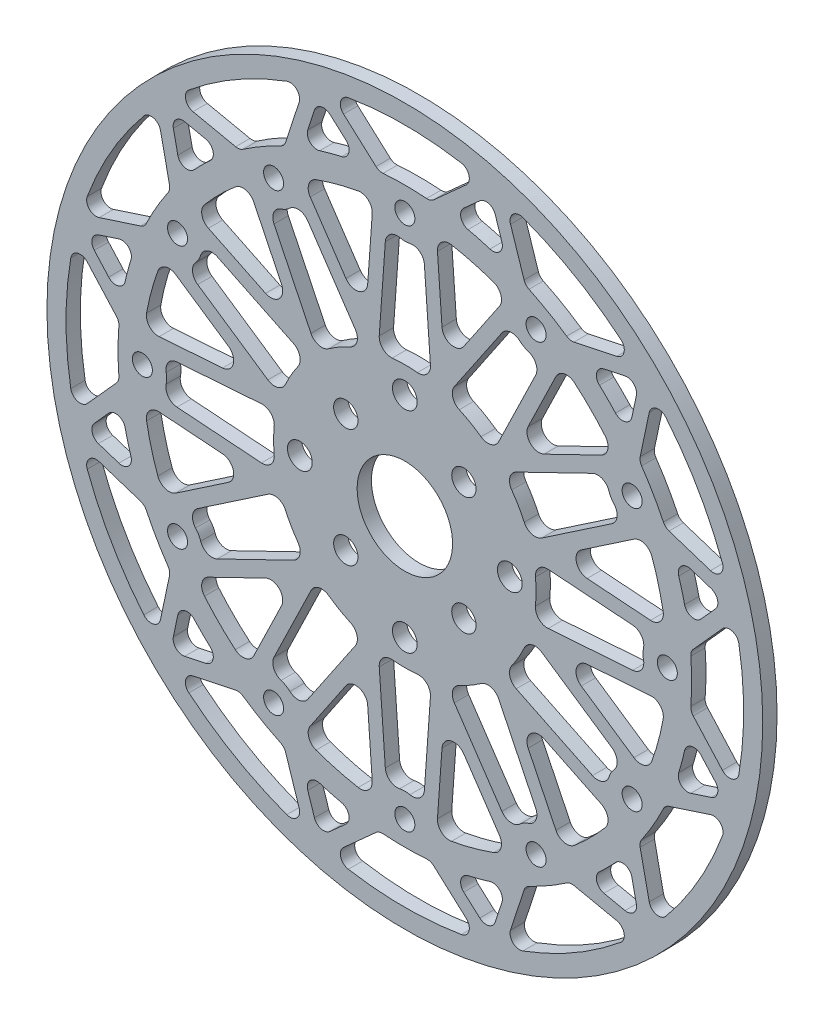
SolidWorks part; units mm, degrees
material "Thornel Mat VMA"
ref_plane "前视基准面" through (0, 0, 0) normal (0, 0, 1) x (1, 0, 0)
ref_plane "上视基准面" through (0, 0, 0) normal (0, 1, 0) x (1, 0, 0)
ref_plane "右视基准面" through (0, 0, 0) normal (1, 0, 0) x (0, 0, -1)
other "Configuration Table"
sketch "草图1" plane through (0, 0, 0) normal (0, 0, 1) x (1, 0, 0)
  circle A0 centre (0, 0) radius 75
  dimension "D1" = 150
extrude "凸台-拉伸1" add sketch "草图1" along normal blind 3
sketch "草图2" plane through (0, 0, 0) normal (0, 0, -1) x (-1, 0, 0)
  line L0 (0, 22) -> (0, 0) construction
  line L1 (0, 0) -> (12.3744, 12.3744) construction
  circle A0 centre (0, 0) radius 55 construction
  circle A1 centre (0, 55) radius 2.1
  circle A2 centre (27.5, 47.6314) radius 2.1
  circle A3 centre (47.6314, 27.5) radius 2.1
  circle A4 centre (55, 0) radius 2.1
  circle A5 centre (47.6314, -27.5) radius 2.1
  circle A6 centre (27.5, -47.6314) radius 2.1
  circle A7 centre (0, -55) radius 2.1
  circle A8 centre (-27.5, -47.6314) radius 2.1
  circle A9 centre (-47.6314, -27.5) radius 2.1
  circle A10 centre (-55, 0) radius 2.1
  circle A11 centre (-47.6314, 27.5) radius 2.1
  circle A12 centre (-27.5, 47.6314) radius 2.1
  circle A13 centre (0, 0) radius 22 construction
  circle A14 centre (0, 0) radius 17.5 construction
  circle A15 centre (0, 22) radius 2.6
  circle A16 centre (12.3744, 12.3744) radius 2.55
  circle A17 centre (22, 0) radius 2.6
  circle A18 centre (12.3744, -12.3744) radius 2.55
  circle A19 centre (0, -22) radius 2.6
  circle A20 centre (-12.3744, -12.3744) radius 2.55
  circle A21 centre (-22, 0) radius 2.6
  circle A22 centre (-12.3744, 12.3744) radius 2.55
  circle A23 centre (0, 0) radius 10
  point P29 (0, 0)
  point P49 (0, 0)
  dimension "D1" = 110
  dimension "D2" = 4.2
  dimension "D4" = 35
  dimension "D5" = 44
  dimension "D6" = 5.2
  dimension "D8" = 5.1
  dimension "D10" = 20
  dimension "D7" = 45
  dimension "D3" = 12
  dimension "D9" = 4
extrude "切除-拉伸1" cut sketch "草图2" against normal blind 3
sketch "草图3" plane through (0, 0, 3) normal (0, 0, 1) x (1, 0, 0)
  line L0 (0, 55) -> (0, -55)
  line L1 (-27.5, 47.6314) -> (27.5, -47.6314)
  line L2 (-27.5, -47.6314) -> (27.5, 47.6314)
  line L3 (-55, 0) -> (55, 0)
  line L4 (-47.6314, 27.5) -> (47.6314, -27.5)
  line L5 (-47.6314, -27.5) -> (47.6314, 27.5)
  circle A0 centre (0, 0) radius 27.5
  circle A1 centre (-47.6314, 27.5) radius 2.1 construction
  circle A2 centre (-55, 0) radius 2.1 construction
  circle A3 centre (-47.6314, -27.5) radius 2.1 construction
  circle A4 centre (-27.5, -47.6314) radius 2.1 construction
  circle A5 centre (0, -55) radius 2.1 construction
  circle A6 centre (27.5, -47.6314) radius 2.1 construction
  circle A7 centre (47.6314, -27.5) radius 2.1 construction
  circle A8 centre (55, 0) radius 2.1 construction
  circle A9 centre (47.6314, 27.5) radius 2.1 construction
  circle A10 centre (27.5, 47.6314) radius 2.1 construction
  circle A11 centre (0, 55) radius 2.1 construction
  circle A12 centre (-27.5, 47.6314) radius 2.1 construction
  circle A13 centre (-47.6314, 27.5) radius 2.1
  circle A14 centre (-55, 0) radius 2.1
  circle A15 centre (-47.6314, -27.5) radius 2.1
  circle A16 centre (-27.5, -47.6314) radius 2.1
  circle A17 centre (0, -55) radius 2.1
  circle A18 centre (27.5, -47.6314) radius 2.1
  circle A19 centre (47.6314, -27.5) radius 2.1
  circle A20 centre (55, 0) radius 2.1
  circle A21 centre (47.6314, 27.5) radius 2.1
  circle A22 centre (27.5, 47.6314) radius 2.1
  circle A23 centre (0, 55) radius 2.1
  circle A24 centre (-27.5, 47.6314) radius 2.1
  circle A25 centre (-27.5, 47.6314) radius 5.1
  circle A26 centre (0, 55) radius 5.1
  circle A27 centre (27.5, 47.6314) radius 5.1
  circle A28 centre (47.6314, 27.5) radius 5.1
  circle A29 centre (55, 0) radius 5.1
  circle A30 centre (47.6314, -27.5) radius 5.1
  circle A31 centre (27.5, -47.6314) radius 5.1
  circle A32 centre (0, -55) radius 5.1
  circle A33 centre (-27.5, -47.6314) radius 5.1
  circle A34 centre (-47.6314, -27.5) radius 5.1
  circle A35 centre (-55, 0) radius 5.1
  circle A36 centre (-47.6314, 27.5) radius 5.1
  circle A37 centre (0, 0) radius 55
  dimension "D1" = 55
  dimension "D2" = 3
extrude "切除-拉伸2" cut sketch "草图3" against normal blind 10 contours A26 A37 A25 L1 A0 L0 | A27 A37 A26 L0 A0 L2 | A28 A37 A27 L2 A0 L5 | A29 A37 A28 L5 A0 L3 | A30 A37 A29 L3 A0 L4 | A31 A37 A30 L4 A0 L1 | A32 A37 A31 L1 A0 L0 | A33 A37 A32 L0 A0 L2 | A34 A37 A33 L2 A0 L5 | A35 A37 A34 L5 A0 L3 | A36 A37 A35 L3 A0 L4 | A25 A37 A36 L4 A0 L1 region at (10.7724, 40.2033, 3) region at (-10.7724, 40.2033, 3) region at (29.4309, 29.4309, 3) region at (-29.4309, 29.4309, 3) region at (10.7724, -40.2033, 3) region at (-10.7724, -40.2033, 3) region at (29.4309, -29.4309, 3) region at (-29.4309, -29.4309, 3) region at (-40.2033, -10.7724, 3) region at (-40.2033, 10.7724, 3) region at (40.2033, 10.7724, 3) region at (40.2033, -10.7724, 3)
sketch "草图4" plane through (0, 0, 3) normal (0, 0, 1) x (1, 0, 0)
  line L0 (-14.235, 53.1259) -> (0, 0) construction
  line L1 (-5.0945, 54.7635) -> (-7.1175, 26.563)
  line L2 (-22.9698, 49.9739) -> (-7.1175, 26.563)
  line L3 (5.0945, 54.7635) -> (7.1175, 26.563)
  line L4 (22.9698, 49.9739) -> (7.1175, 26.563)
  line L5 (31.7938, 44.8794) -> (19.4454, 19.4454)
  line L6 (44.8794, 31.7938) -> (19.4454, 19.4454)
  line L7 (49.9739, 22.9698) -> (26.563, 7.1175)
  line L8 (54.7635, 5.0945) -> (26.563, 7.1175)
  line L9 (54.7635, -5.0945) -> (26.563, -7.1175)
  line L10 (49.9739, -22.9698) -> (26.563, -7.1175)
  line L11 (44.8794, -31.7938) -> (19.4454, -19.4454)
  line L12 (31.7938, -44.8794) -> (19.4454, -19.4454)
  line L13 (22.9698, -49.9739) -> (7.1175, -26.563)
  line L14 (5.0945, -54.7635) -> (7.1175, -26.563)
  line L15 (-5.0945, -54.7635) -> (-7.1175, -26.563)
  line L16 (-22.9698, -49.9739) -> (-7.1175, -26.563)
  line L17 (-31.7938, -44.8794) -> (-19.4454, -19.4454)
  line L18 (-44.8794, -31.7938) -> (-19.4454, -19.4454)
  line L19 (-49.9739, -22.9698) -> (-26.563, -7.1175)
  line L20 (-54.7635, -5.0945) -> (-26.563, -7.1175)
  line L21 (-54.7635, 5.0945) -> (-26.563, 7.1175)
  line L22 (-49.9739, 22.9698) -> (-26.563, 7.1175)
  line L23 (-44.8794, 31.7938) -> (-19.4454, 19.4454)
  line L24 (-31.7938, 44.8794) -> (-19.4454, 19.4454)
  line L25 (0, 0) -> (-7.1175, 26.563) construction
  arc A0 (-5.0945, 54.7635) -> (-22.9698, 49.9739) centre (0, 0) ccw construction
  dimension "D2" = 27.5
  dimension "D1" = 12
extrude "拉伸-薄壁1" add sketch "草图4" against normal blind 3 thin thin type mid plane wall 3
fillet "圆角1" radius 2.5 84 edges at (21.5762, 50.5912, 1.5) (8.3038, 30.9902, 1.5) (6.61, 54.6014, 1.5) (5.5876, 26.9264, 1.5) (-3.8164, 51.6169, 1.5) (3.8164, 51.6169, 1.5) (43.9812, 33.0251, 1.5) (22.6864, 22.6864, 1.5) (33.0251, 43.9812, 1.5) (8.6242, 26.1127, 1.5) (22.5034, 46.6098, 1.5) (29.1136, 42.7934, 1.5) (18.3022, 20.5251, 1.5) (54.6014, 6.61, 1.5) (30.9902, 8.3038, 1.5) (50.5912, 21.5762, 1.5) (20.5251, 18.3022, 1.5) (42.7934, 29.1136, 1.5) (46.6098, 22.5034, 1.5) (26.1127, 8.6242, 1.5) (50.5912, -21.5762, 1.5) (30.9902, -8.3038, 1.5) (54.6014, -6.61, 1.5) (26.9264, 5.5876, 1.5) (51.6169, 3.8164, 1.5) (51.6169, -3.8164, 1.5) (26.9264, -5.5876, 1.5) (33.0251, -43.9812, 1.5) (22.6864, -22.6864, 1.5) (43.9812, -33.0251, 1.5) (26.1127, -8.6242, 1.5) (46.6098, -22.5034, 1.5) (42.7934, -29.1136, 1.5) (20.5251, -18.3022, 1.5) (6.61, -54.6014, 1.5) (8.3038, -30.9902, 1.5) (21.5762, -50.5912, 1.5) (18.3022, -20.5251, 1.5) (29.1136, -42.7934, 1.5) (22.5034, -46.6098, 1.5) (8.6242, -26.1127, 1.5) (-21.5762, -50.5912, 1.5) (-8.3038, -30.9902, 1.5) (-6.61, -54.6014, 1.5) (5.5876, -26.9264, 1.5) (3.8164, -51.6169, 1.5) (-3.8164, -51.6169, 1.5) (-5.5876, -26.9264, 1.5) (-43.9812, -33.0251, 1.5) (-22.6864, -22.6864, 1.5) (-33.0251, -43.9812, 1.5) (-8.6242, -26.1127, 1.5) (-22.5034, -46.6098, 1.5) (-29.1136, -42.7934, 1.5) (-18.3022, -20.5251, 1.5) (-54.6014, -6.61, 1.5) (-30.9902, -8.3038, 1.5) (-50.5912, -21.5762, 1.5) (-20.5251, -18.3022, 1.5) (-42.7934, -29.1136, 1.5) (-46.6098, -22.5034, 1.5) (-26.1127, -8.6242, 1.5) (-50.5912, 21.5762, 1.5) (-30.9902, 8.3038, 1.5) (-54.6014, 6.61, 1.5) (-26.9264, -5.5876, 1.5) (-51.6169, -3.8164, 1.5) (-51.6169, 3.8164, 1.5) (-26.9264, 5.5876, 1.5) (-33.0251, 43.9812, 1.5) (-22.6864, 22.6864, 1.5) (-43.9812, 33.0251, 1.5) (-29.1136, 42.7934, 1.5) (-22.5034, 46.6098, 1.5) (-8.6242, 26.1127, 1.5) (-18.3022, 20.5251, 1.5) (-26.1127, 8.6242, 1.5) (-46.6098, 22.5034, 1.5) (-42.7934, 29.1136, 1.5) (-20.5251, 18.3022, 1.5) (-5.5876, 26.9264, 1.5) (-8.3038, 30.9902, 1.5) (-21.5762, 50.5912, 1.5) (-6.61, 54.6014, 1.5)
sketch "草图5" plane through (0, 0, 3) normal (0, 0, 1) x (1, 0, 0)
  circle A2 centre (0, 0) radius 71
  circle A3 centre (0, 0) radius 71
  circle A111 centre (-55, 0) radius 2.1 construction
  circle A112 centre (-47.6314, -27.5) radius 2.1 construction
  circle A113 centre (-27.5, -47.6314) radius 2.1 construction
  circle A114 centre (0, -55) radius 2.1 construction
  circle A115 centre (27.5, -47.6314) radius 2.1 construction
  circle A116 centre (47.6314, -27.5) radius 2.1 construction
  circle A117 centre (55, 0) radius 2.1 construction
  circle A118 centre (47.6314, 27.5) radius 2.1 construction
  circle A119 centre (27.5, 47.6314) radius 2.1 construction
  circle A120 centre (0, 55) radius 2.1 construction
  circle A121 centre (-27.5, 47.6314) radius 2.1 construction
  circle A122 centre (-47.6314, 27.5) radius 2.1 construction
  circle A123 centre (-55, 0) radius 2.1
  circle A124 centre (-47.6314, -27.5) radius 2.1
  circle A125 centre (-27.5, -47.6314) radius 2.1
  circle A126 centre (0, -55) radius 2.1
  circle A127 centre (27.5, -47.6314) radius 2.1
  circle A128 centre (47.6314, -27.5) radius 2.1
  circle A129 centre (55, 0) radius 2.1
  circle A130 centre (47.6314, 27.5) radius 2.1
  circle A131 centre (27.5, 47.6314) radius 2.1
  circle A132 centre (0, 55) radius 2.1
  circle A133 centre (-27.5, 47.6314) radius 2.1
  circle A134 centre (-47.6314, 27.5) radius 2.1
  circle A135 centre (-47.6314, 27.5) radius 5.1
  circle A136 centre (-27.5, 47.6314) radius 5.1
  circle A137 centre (0, 55) radius 5.1
  circle A138 centre (27.5, 47.6314) radius 5.1
  circle A139 centre (47.6314, 27.5) radius 5.1
  circle A140 centre (55, 0) radius 5.1
  circle A141 centre (47.6314, -27.5) radius 5.1
  circle A142 centre (27.5, -47.6314) radius 5.1
  circle A143 centre (0, -55) radius 5.1
  circle A144 centre (-27.5, -47.6314) radius 5.1
  circle A145 centre (-47.6314, -27.5) radius 5.1
  circle A146 centre (-55, 0) radius 5.1
  circle A147 centre (0, 0) radius 60.1
  dimension "D1" = 4
  dimension "D2" = 3
extrude "切除-拉伸3" cut sketch "草图5" against normal blind 3 contours A3 A147 region at (-68.9918, 0, 3)
sketch "草图7" plane through (0, 0, 3) normal (0, 0, 1) x (1, 0, 0)
  line L0 (0, 0) -> (-14.235, 53.1259) construction
  line L1 (-14.235, 53.1259) -> (-19.4114, 72.4444) construction
  line L2 (-26.8491, 49.628) -> (-19.4114, 72.4444)
  line L3 (-19.4114, 72.4444) -> (-1.562, 56.4037)
  line L4 (1.562, 56.4037) -> (19.4114, 72.4444)
  line L5 (19.4114, 72.4444) -> (26.8491, 49.628)
  line L6 (29.5545, 48.066) -> (53.033, 53.033)
  line L7 (53.033, 53.033) -> (48.066, 29.5545)
  line L8 (49.628, 26.8491) -> (72.4444, 19.4114)
  line L9 (72.4444, 19.4114) -> (56.4037, 1.562)
  line L10 (56.4037, -1.562) -> (72.4444, -19.4114)
  line L11 (72.4444, -19.4114) -> (49.628, -26.8491)
  line L12 (48.066, -29.5545) -> (53.033, -53.033)
  line L13 (53.033, -53.033) -> (29.5545, -48.066)
  line L14 (26.8491, -49.628) -> (19.4114, -72.4444)
  line L15 (19.4114, -72.4444) -> (1.562, -56.4037)
  line L16 (-1.562, -56.4037) -> (-19.4114, -72.4444)
  line L17 (-19.4114, -72.4444) -> (-26.8491, -49.628)
  line L18 (-29.5545, -48.066) -> (-53.033, -53.033)
  line L19 (-53.033, -53.033) -> (-48.066, -29.5545)
  line L20 (-49.628, -26.8491) -> (-72.4444, -19.4114)
  line L21 (-72.4444, -19.4114) -> (-56.4037, -1.562)
  line L22 (-56.4037, 1.562) -> (-72.4444, 19.4114)
  line L23 (-72.4444, 19.4114) -> (-49.628, 26.8491)
  line L24 (-48.066, 29.5545) -> (-53.033, 53.033)
  line L25 (-53.033, 53.033) -> (-29.5545, 48.066)
  line L26 (0, 0) -> (-1.562, 56.4037) construction
  line L27 (0, 0) -> (26.8491, 49.628) construction
  arc A0 (-9.7712, 54.1251) -> (-18.6004, 51.7593) centre (0, 0) ccw construction
  circle A1 centre (0, 0) radius 75 construction
  circle A2 centre (0, 55) radius 2.1 construction
  circle A3 centre (-27.5, 47.6314) radius 2.1 construction
  circle A4 centre (0, 55) radius 2.1
  circle A5 centre (-27.5, 47.6314) radius 2.1
  dimension "D1" = 66.11
  dimension "D3" = 30
  dimension "D4" = 56.4253
  dimension "D2" = 12
extrude "拉伸-薄壁3" add sketch "草图7" against normal blind 3 thin contours L24 L25 | L2 L3 | L4 L5 | L6 L7 | L8 L9 | L10 L11 | L12 L13 | L14 L15 | L16 L17 | L18 L19 | L20 L21 | L22 L23 thin type one direction wall 3
fillet "圆角2" radius 2 84 edges at (-49.1438, 49.1438, 1.5) (-46.7399, 37.7808, 1.5) (-37.7808, 46.7399, 1.5) (-9.3492, 59.3684, 1.5) (-17.9879, 67.1317, 1.5) (-21.5876, 56.0891, 1.5) (-48.3068, 52.0332, 1.5) (-34.6084, 49.1352, 1.5) (-25.2481, 54.5394, 1.5) (-20.9086, 67.8515, 1.5) (17.9879, 67.1317, 1.5) (9.3492, 59.3684, 1.5) (21.5876, 56.0891, 1.5) (-15.8184, 69.2155, 1.5) (-5.4041, 59.8565, 1.5) (5.4041, 59.8565, 1.5) (15.8184, 69.2155, 1.5) (49.1438, 49.1438, 1.5) (37.7808, 46.7399, 1.5) (46.7399, 37.7808, 1.5) (20.9086, 67.8515, 1.5) (25.2481, 54.5394, 1.5) (34.6084, 49.1352, 1.5) (48.3068, 52.0332, 1.5) (67.1317, 17.9879, 1.5) (56.0891, 21.5876, 1.5) (59.3684, 9.3492, 1.5) (52.0332, 48.3068, 1.5) (49.1352, 34.6084, 1.5) (54.5394, 25.2481, 1.5) (67.8515, 20.9086, 1.5) (67.1317, -17.9879, 1.5) (59.3684, -9.3492, 1.5) (56.0891, -21.5876, 1.5) (69.2155, 15.8184, 1.5) (59.8565, 5.4041, 1.5) (59.8565, -5.4041, 1.5) (69.2155, -15.8184, 1.5) (49.1438, -49.1438, 1.5) (46.7399, -37.7808, 1.5) (37.7808, -46.7399, 1.5) (67.8515, -20.9086, 1.5) (54.5394, -25.2481, 1.5) (49.1352, -34.6084, 1.5) (52.0332, -48.3068, 1.5) (17.9879, -67.1317, 1.5) (21.5876, -56.0891, 1.5) (9.3492, -59.3684, 1.5) (48.3068, -52.0332, 1.5) (34.6084, -49.1352, 1.5) (25.2481, -54.5394, 1.5) (20.9086, -67.8515, 1.5) (-17.9879, -67.1317, 1.5) (-9.3492, -59.3684, 1.5) (-21.5876, -56.0891, 1.5) (15.8184, -69.2155, 1.5) (5.4041, -59.8565, 1.5) (-5.4041, -59.8565, 1.5) (-15.8184, -69.2155, 1.5) (-49.1438, -49.1438, 1.5) (-37.7808, -46.7399, 1.5) (-46.7399, -37.7808, 1.5) (-20.9086, -67.8515, 1.5) (-25.2481, -54.5394, 1.5) (-34.6084, -49.1352, 1.5) (-48.3068, -52.0332, 1.5) (-67.1317, -17.9879, 1.5) (-56.0891, -21.5876, 1.5) (-59.3684, -9.3492, 1.5) (-52.0332, -48.3068, 1.5) (-49.1352, -34.6084, 1.5) (-54.5394, -25.2481, 1.5) (-67.8515, -20.9086, 1.5) (-49.1352, 34.6084, 1.5) (-67.8515, 20.9086, 1.5) (-54.5394, 25.2481, 1.5) (-67.1317, 17.9879, 1.5) (-59.3684, 9.3492, 1.5) (-56.0891, 21.5876, 1.5) (-69.2155, -15.8184, 1.5) (-59.8565, -5.4041, 1.5) (-59.8565, 5.4041, 1.5) (-69.2155, 15.8184, 1.5) (-52.0332, 48.3068, 1.5)
